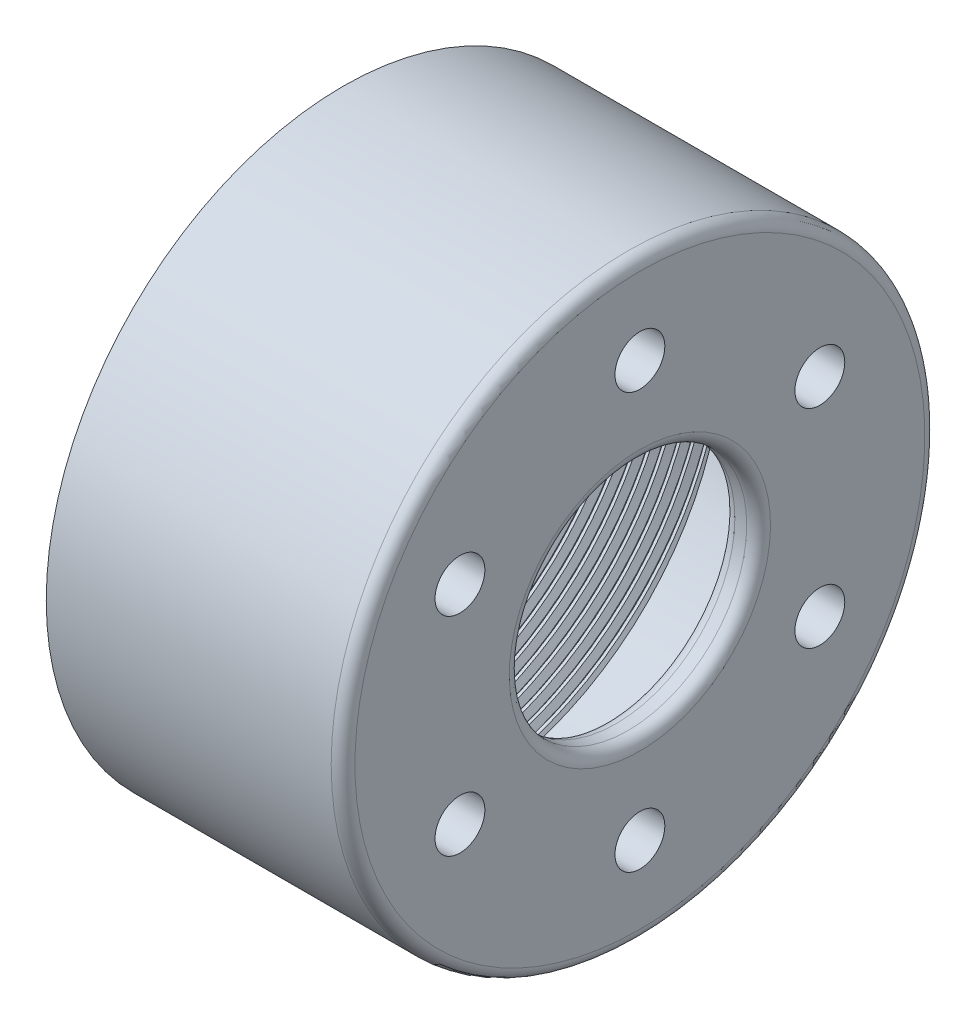
SolidWorks part; units mm, degrees
ref_plane "Front Plane" through (0, 0, 0) normal (0, 0, 1) x (1, 0, 0)
ref_plane "Top Plane" through (0, 0, 0) normal (0, 1, 0) x (1, 0, 0)
ref_plane "Right Plane" through (0, 0, 0) normal (1, 0, 0) x (0, 0, -1)
sketch "Sketch1" plane through (0, 0, 0) normal (0, 0, 1) x (1, 0, 0)
  line L0 (0, 1) -> (0, 14)
  line L1 (-1, 15) -> (-25, 15)
  line L2 (-25, 15) -> (-25, 13)
  line L3 (-25, 13) -> (-15, 13)
  line L4 (-3, 11) -> (-3, 1)
  line L5 (-2, 0) -> (-1, 0)
  line L6 (-15, 13) -> (-15, 12)
  line L7 (-15, 12) -> (-4, 12)
  line L8 (0, 0) -> (0, -10)
  line L9 (0, -10) -> (-37.136, -10) construction
  arc A0 (-4, 12) -> (-3, 11) centre (-4, 11) cw
  arc A1 (-3, 1) -> (-2, 0) centre (-2, 1) ccw
  arc A2 (-1, 0) -> (0, 1) centre (-1, 1) ccw
  arc A3 (0, 14) -> (-1, 15) centre (-1, 14) ccw
  point P16 (-3, 0)
  point P22 (0, 15)
  dimension "D9" = 1
  dimension "D1" = 3
  dimension "D2" = 15
  dimension "D3" = 3
  dimension "D4" = 2
  dimension "D5" = 15
  dimension "D6" = 25
  dimension "D7" = 10
  dimension "D8" = 10
revolve "Revolve1" add sketch "Sketch1" angle 360 about L9 region at (-0.499, 0.499, 0)
thread "Thread1" pitch 1 method cut profile "Thread Profile1" start angle 0, offset 0, length 10, pitch 1, diameter 46
ref_plane "Plane1" through (-25, -10, -23) normal (0, -1, 0) x (0, 0, -1)
sketch "Thread Profile1" plane through (-25, -10, -23) normal (0, -1, 0) x (0, 0, -1)
  line L0 (0, 0) -> (0, 1) construction
  line L1 (0, 0) -> (0.5413, 0.3125)
  line L2 (0.5413, 0.3125) -> (0.5413, 0.4375)
  line L3 (0.5413, 0.4375) -> (0, 0.75)
  line L4 (0.5413, 0.375) -> (0, 0.375) construction
  line L11 (0, 0) -> (0, 0.75)
  point P2 (0, 0)
  dimension "Pitch" = 1
  dimension "Profile_Angle" = 60
  dimension "Profile_Land" = 0.125
  dimension "Profile_Height" = 0.5413
sketch "Sketch8" plane through (0, 0, 0) normal (1, 0, 0) x (0, 0, -1)
  circle A0 centre (0, -10) radius 11 construction
  circle A1 centre (0, -10) radius 24 construction
  point P0 (0, 7.5)
  dimension "D1" = 17.5
  dimension "D2" = 17.5
hole_wizard "Tap Drill for M5x0.8 Tap1" positions "Sketch8" profile "Sketch7" hole size "M5x0.8" standard "ANSI Metric" end condition through all
sketch "Sketch7" plane through (0, 7.5, 0) normal (0, 1, 0) x (0, 0, -1)
  line L0 (0, 0) -> (0, 25)
  line L1 (0, 25) -> (2.1, 25)
  line L2 (2.1, 25) -> (2.1, 0)
  line L5 (2.1, 0) -> (0, 0)
  line L11 (0, -6.35) -> (0, 107.95) construction
  dimension "Thru Hole Dia." = 4.2
  dimension "Thru Hole Depth" = 25
pattern_circular "CirPattern1" count 6 over 360 about axis through (0, -10, 0) along (1, 0, 0) of "Tap Drill for M5x0.8 Tap1"
